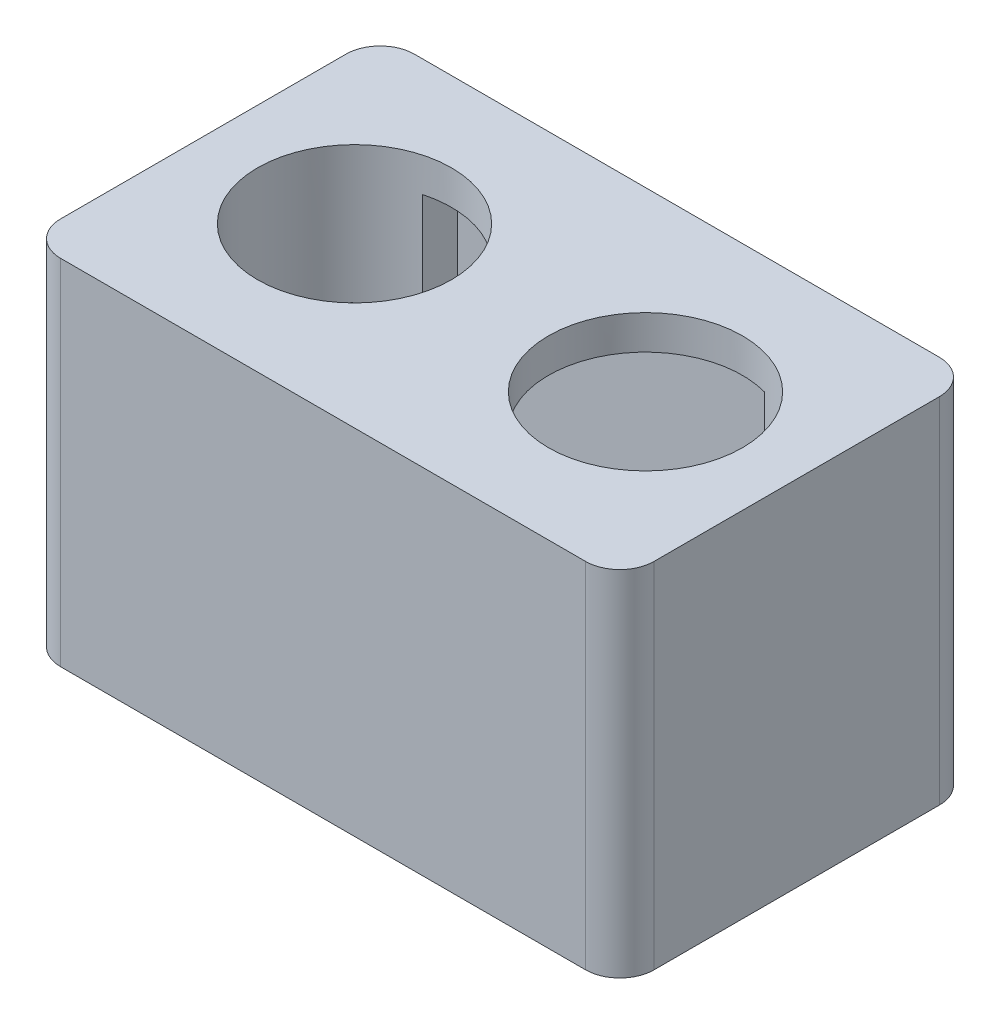
SolidWorks part; units mm, degrees
ref_plane "Alzado" through (0, 0, 0) normal (0, 0, 1) x (1, 0, 0)
ref_plane "Planta" through (0, 0, 0) normal (0, 1, 0) x (1, 0, 0)
ref_plane "Vista lateral" through (0, 0, 0) normal (1, 0, 0) x (0, 0, -1)
sketch "Croquis1" plane through (0, 0, 0) normal (0, 1, 0) x (1, 0, 0)
  line L1 (-23, 12.5) -> (23, 12.5)
  line L2 (-23, 12.5) -> (-23, -12.5)
  line L3 (-23, -12.5) -> (23, -12.5)
  line L4 (23, 12.5) -> (23, -12.5)
  line L5 (-26, 15.5) -> (26, 15.5)
  line L6 (-26, 15.5) -> (-26, -15.5)
  line L7 (-26, -15.5) -> (26, -15.5)
  line L8 (26, 15.5) -> (26, -15.5)
  point P4 (0, 12.5)
  point P6 (23, 0)
  dimension "D1" = 25
  dimension "D2" = 46
  dimension "D3" = 3
  dimension "D4" = 3
  dimension "D5" = 3
  dimension "D6" = 3
extrude "Saliente-Extruir1" add sketch "Croquis1" along normal blind 31 contours L4 L1 L2 L3 | L8 L5 L6 L7 L1 L4 L3 L2 | L2 L1 L4 L3 | L6 L5 L8 L7 region at (0, 0, 0) region at (0, 0, -14.8946)
sketch "Croquis2" plane through (0, 31, 0) normal (0, 1, 0) x (1, 0, 0)
  line L0 (-21.25, 7.6512) -> (-21.25, -6.0971) construction
  line L1 (21.25, 10.5204) -> (21.25, -9.4445) construction
  line L2 (26, 15.5) -> (26, -15.5) construction
  line L3 (-12.75, 0) -> (12.75, 0) construction
  line L4 (-26, 15.5) -> (26, 15.5) construction
  circle A0 centre (-12.75, 0) radius 8.5
  circle A1 centre (12.75, 0) radius 8.5
  point P10 (26, 0)
  point P11 (0, 0)
  point P14 (0, 15.5)
  dimension "D1" = 17
  dimension "D2" = 42.5
extrude "Cortar-Extruir1" cut sketch "Croquis2" against normal blind 31
fillet "Redondeo1" radius 3 4 edges at (-26, 15.5, 15.5) (-26, 15.5, -15.5) (26, 15.5, 15.5) (26, 15.5, -15.5)
shell "Vaciado1" thickness 3 removed face at (-12.75, 0, 8.5)
sketch "Croquis3" plane through (0, 0, 0) normal (0, -1, 0) x (1, 0, 0)
  line L1 (23, -12.5) -> (-23, -12.5)
  line L2 (23, -12.5) -> (23, 12.5)
  line L3 (23, 12.5) -> (-23, 12.5)
  line L4 (-23, -12.5) -> (-23, 12.5)
extrude "Cortar-Extruir2" cut sketch "Croquis3" against normal blind 19
sketch "Croquis4" plane through (0, 19, 0) normal (0, -1, 0) x (1, 0, 0)
  line L1 (-15, 11.5) -> (15, 11.5)
  line L2 (-15, 11.5) -> (-15, -11.5)
  line L3 (-15, -11.5) -> (15, -11.5)
  line L4 (15, 11.5) -> (15, -11.5)
  point P4 (0, -11.5)
  point P6 (15, 0)
  dimension "D1" = 30
  dimension "D2" = 23
extrude "Cortar-Extruir3" cut sketch "Croquis4" against normal up to surface (9 mm away) up to face at (0, 28, 0)
